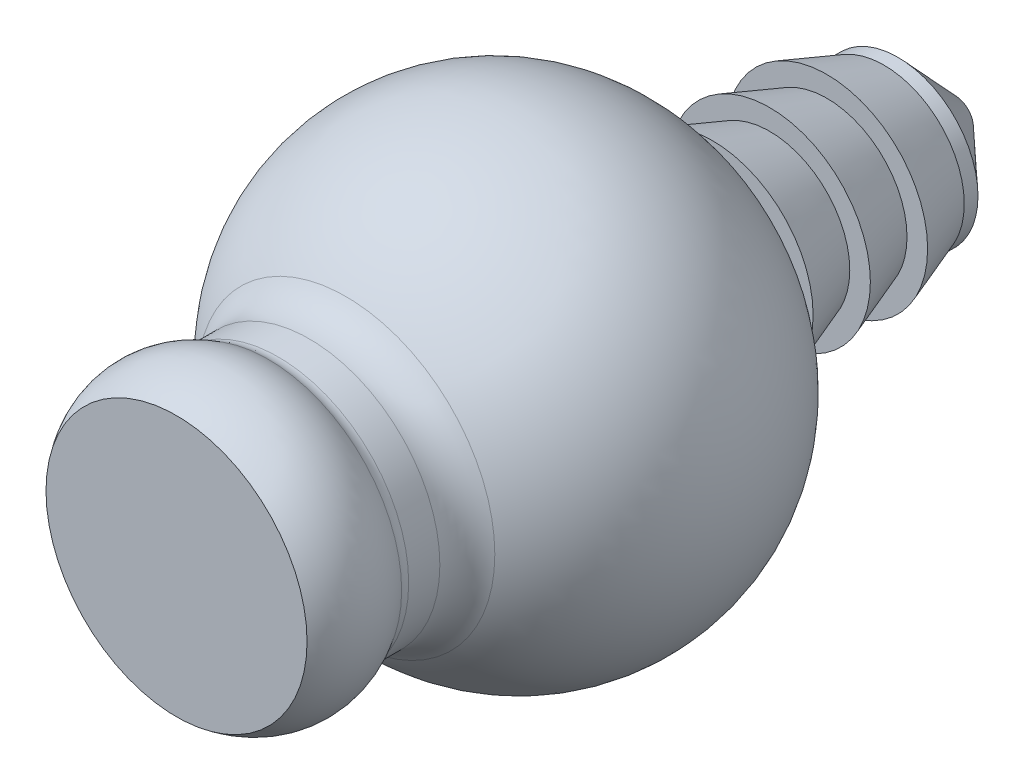
SolidWorks part; units mm, degrees
material "Латунь"
ref_plane "Front" through (0, 0, 0) normal (0, 0, 1) x (1, 0, 0)
ref_plane "Top" through (0, 0, 0) normal (0, 1, 0) x (1, 0, 0)
ref_plane "Right" through (0, 0, 0) normal (1, 0, 0) x (0, 0, -1)
ref_axis "Ось1" through (0, 0, 50) along (0, 0, -1)
sketch "Эскиз1" plane through (0, 0, 0) normal (0, 1, 0) x (1, 0, 0)
  line L0 (0, -10.7) -> (0, 6.3)
  line L1 (0, 6.3) -> (-0.4, 6.3)
  line L2 (-0.4, 6.3) -> (-1.75, 5.05)
  line L3 (-1.75, 5.05) -> (-1.75, 4.75)
  line L4 (-1.75, 4.75) -> (-2.2, 3.5)
  line L5 (-2.2, 3.5) -> (-1.75, 3.5)
  line L6 (-1.75, 3.5) -> (-2.2, 2.25)
  line L7 (-2.2, 2.25) -> (-1.75, 2.25)
  line L8 (-1.75, 2.25) -> (-2.2, 1)
  line L9 (-2.2, 1) -> (-1.75, 1)
  line L10 (-1.75, 1) -> (-1.75, 0)
  line L11 (-1.75, 0) -> (-3.25, 0)
  line L12 (-2.85, -7.8) -> (-2.85, -8.4808)
  line L13 (-2.85, -10.7) -> (0, -10.7)
  line L14 (0, 6.3) -> (0, 9.6978) construction
  line L15 (-2.2, 1) -> (-2.2, 3.5) construction
  line L16 (-1.75, 2.25) -> (-1.75, 4.75) construction
  line L17 (-5, -4.7697) -> (-5, -2.1861) construction
  line L18 (-3.2, -10.3865) -> (-3.2, -9.1467) construction
  arc A0 (-3.25, 0) -> (-3.25, -7) centre (-0.625, -3.5) ccw
  arc A1 (-3.25, -7) -> (-2.85, -7.8) centre (-3.85, -7.8) cw
  arc A2 (-2.85, -8.4808) -> (-2.9154, -8.7) centre (-3.25, -8.4808) cw
  arc A3 (-2.9154, -8.7) -> (-2.85, -10.7) centre (-1.4604, -9.6535) ccw
  point P26 (-5, -3.5)
  point P27 (-3.2, -9.6535)
  dimension "D1" = 0.8
  dimension "D2" = 3.5
  dimension "D3" = 4.4
  dimension "D4" = 2.5
  dimension "D5" = 1
  dimension "D6" = 6.3
  dimension "D7" = 0.3
  dimension "D8" = 10
  dimension "D9" = 6.5
  dimension "D10" = 17
  dimension "D11" = 5.7
  dimension "D12" = 7
  dimension "D13" = 6.4
  dimension "D14" = 2
revolve "Повернуть2" add sketch "Эскиз1" angle 360 about L14
